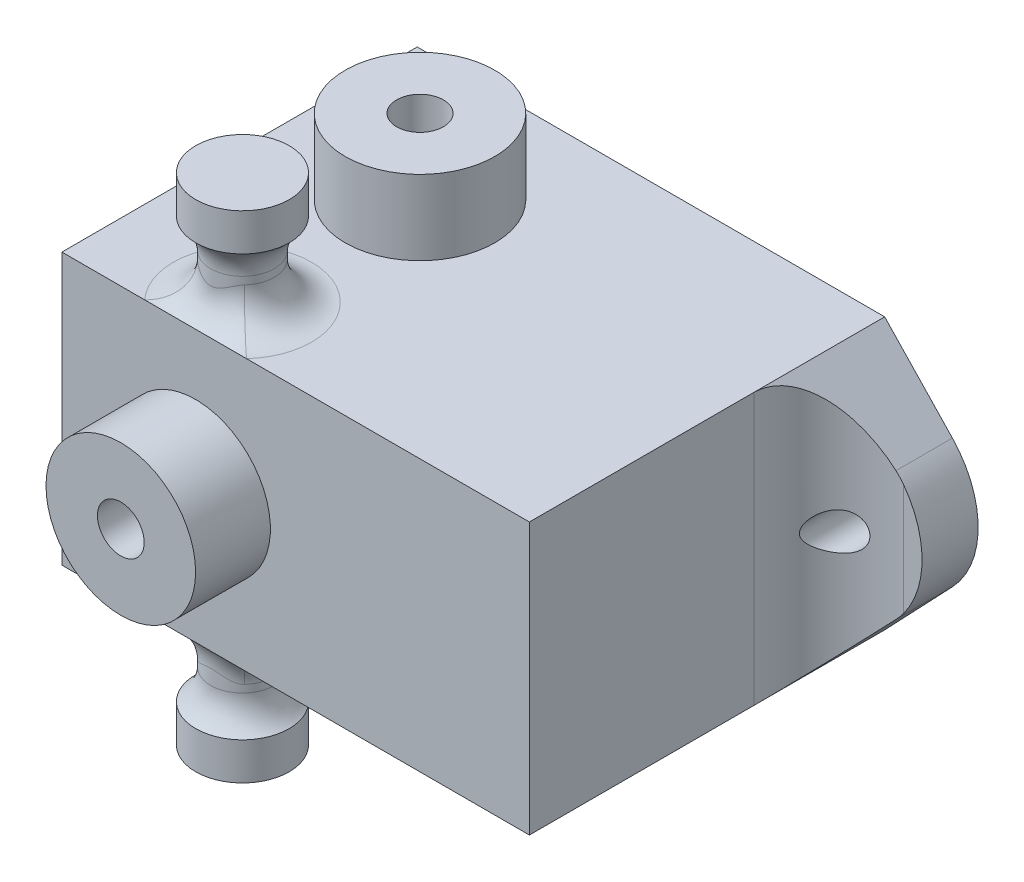
SolidWorks part; units mm, degrees
ref_plane "Спереди" through (0, 0, 0) normal (0, 0, 1) x (1, 0, 0)
ref_plane "Сверху" through (0, 0, 0) normal (0, 1, 0) x (1, 0, 0)
ref_plane "Справа" through (0, 0, 0) normal (1, 0, 0) x (0, 0, -1)
sketch "Эскиз1" plane through (0, 0, 0) normal (0, 1, 0) x (1, 0, 0)
  line L1 (-23, 17) -> (-24, 17)
  line L4 (-24, 17) -> (-24, -2)
  line L5 (-24, -2) -> (1, -2)
  line L6 (1, -2) -> (1, 17)
  line L7 (1, 17) -> (0, 17)
  line L8 (-23, 17) -> (0, 17)
extrude "Бобышка-Вытянуть1" add sketch "Эскиз1" along normal blind 14.5
sketch "Эскиз2" plane through (0, 0, -17) normal (0, 0, -1) x (-1, 0, 0)
  line L0 (11.5, 14.5) -> (11.5, 13.5) construction
  line L1 (-1, 14.5) -> (24, 14.5) construction
  line L2 (11.5, 13.5) -> (0, 13.5)
  line L3 (0, 13.5) -> (0, 1)
  line L4 (0, 1) -> (23, 1)
  line L5 (23, 1) -> (23, 13.5)
  line L6 (23, 13.5) -> (11.5, 13.5)
extrude "Вырез-Вытянуть1" cut sketch "Эскиз2" against normal blind 17
sketch "Эскиз4" plane through (0, 0, -17) normal (0, 0, -1) x (-1, 0, 0)
  line L0 (24, 14.5) -> (24, 0) construction
  line L1 (24, 14.5) -> (27.6206, 10.6956)
  line L2 (24, 0) -> (27.6206, 3.8044)
  line L3 (24, 14.5) -> (24, 0)
  arc A0 (27.6206, 3.8044) -> (27.6206, 10.6956) centre (24, 7.25) ccw
extrude "Бобышка-Вытянуть3" add sketch "Эскиз4" against normal blind 3
ref_plane "Плоскость1" through (-11.5, 0, 0) normal (-1, 0, 0) x (0, 0, 1)
mirror "Зеркальное отражение2" about plane through (-11.5, 0, 0) normal (-1, 0, 0) of "Бобышка-Вытянуть3"
fillet "Скругление1" radius 4 2 edges
sketch "Эскиз5" plane through (0, 14.5, 0) normal (0, 1, 0) x (1, 0, 0)
  line L0 (-17.0069, 17) -> (-17.0069, 10) construction
  line L1 (1, 17) -> (-24, 17) construction
  line L2 (-24, 7.877) -> (-16.85, 7.877) construction
  line L3 (-24, 10) -> (-24, -2) construction
  line L4 (-17.0069, 10) -> (-20.8312, 10) construction
  line L5 (-16.85, 7.877) -> (-16.85, 9.1229) construction
  circle A0 centre (-16.85, 10) radius 4
  dimension "D1" = 7.15
  dimension "D2" = 7
extrude "Бобышка-Вытянуть4" add sketch "Эскиз5" along normal blind 4
sketch "Эскиз6" plane through (0, 18.5, 0) normal (0, 1, 0) x (1, 0, 0)
  circle A0 centre (-16.85, 10) radius 1.25
extrude "Вырез-Вытянуть2" cut sketch "Эскиз6" against normal through all
ref_plane "Плоскость2" through (0, 7.25, 0) normal (0, -1, 0) x (-1, 0, 0)
mirror "Зеркальное отражение3" about plane through (0, 7.25, 0) normal (0, -1, 0) of "Вырез-Вытянуть2", "Бобышка-Вытянуть4"
sketch "Эскиз7" plane through (0, 0, 2) normal (0, 0, 1) x (1, 0, 0)
  line L0 (-16.85, 18.5) -> (-16.85, -4)
  line L1 (-15.6, 18.5) -> (-18.1, 18.5) construction
  line L2 (-20.85, -4) -> (-12.85, -4) construction
  circle A0 centre (-16.85, 7.25) radius 4
extrude "Бобышка-Вытянуть5" add sketch "Эскиз7" along normal blind 4 contours L0 A0 | L0 A0
sketch "Эскиз8" plane through (0, 0, 6) normal (0, 0, 1) x (1, 0, 0)
  circle A0 centre (-16.85, 7.25) radius 1.25
extrude "Вырез-Вытянуть3" cut sketch "Эскиз8" against normal through all
sketch "Эскиз9" plane through (0, 14.5, 0) normal (0, 1, 0) x (1, 0, 0)
  line L0 (-16.85, 10) -> (-16.85, -2) construction
  line L1 (-16.85, -6) -> (-16.85, -2) construction
  line L2 (-24, -2) -> (1, -2) construction
  line L4 (-16.85, -2) -> (-16.85, 0.5057) construction
  circle A0 centre (-16.85, 0.5057) radius 1.7
extrude "Бобышка-Вытянуть6" add sketch "Эскиз9" along normal blind 4
sketch "Эскиз13" plane through (0, 18.5, 0) normal (0, 1, 0) x (1, 0, 0)
  circle A0 centre (-16.85, 0.5057) radius 2.5
extrude "Бобышка-Вытянуть7" add sketch "Эскиз13" along normal blind 2
fillet "Скругление2" radius 2 1 edges at (-16.85, 14.5, 1.1943)
fillet "Скругление3" radius 2 1 edges at (-16.85, 18.5, 1.1943)
mirror "Зеркальное отражение4" about plane through (0, 7.25, 0) normal (0, -1, 0) of "Бобышка-Вытянуть7", "Бобышка-Вытянуть6"
fillet "Скругление4" radius 2 2 edges at (-15.15, -4, -0.5057) (-16.85, 0, 1.1943)
sketch "Эскиз12" plane through (0, 0, -17) normal (0, 0, -1) x (-1, 0, 0)
  line L0 (0, 7.25) -> (-2.5, 7.25) construction
  line L1 (0, 13.5) -> (0, 1) construction
  line L2 (-9.35, 7.25) -> (9.35, 7.25) construction
  line L3 (23, 7.25) -> (25.5, 7.25) construction
  line L4 (23, 1) -> (23, 13.5) construction
  circle A0 centre (-2.5, 7.25) radius 1
  circle A1 centre (25.5, 7.25) radius 1
extrude "Вырез-Вытянуть5" cut sketch "Эскиз12" against normal blind 10
